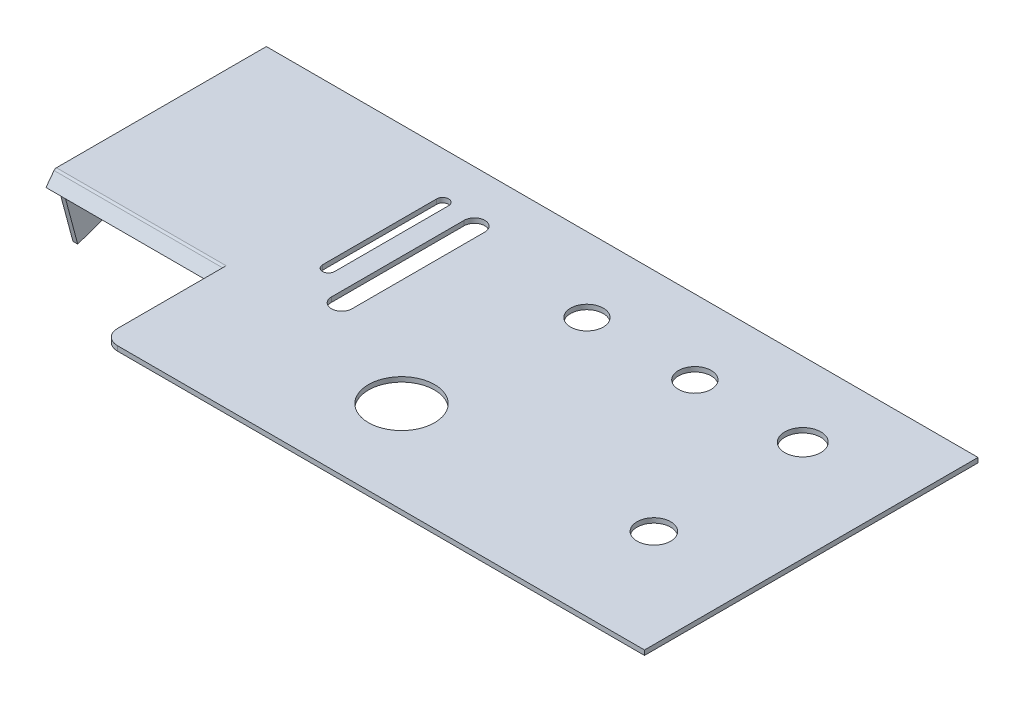
SolidWorks part; units mm, degrees
ref_plane "Front Plane" through (0, 0, 0) normal (0, 0, 1) x (1, 0, 0)
ref_plane "Top Plane" through (0, 0, 0) normal (0, 1, 0) x (1, 0, 0)
ref_plane "Right Plane" through (0, 0, 0) normal (1, 0, 0) x (0, 0, -1)
sketch "Sketch1" plane through (0, 0, 0) normal (0, 1, 0) x (1, 0, 0)
  line L0 (-101.3722, -12.5155) -> (-44.3722, -12.5155) construction
  line L1 (-44.3722, -53.5155) -> (137.6278, -53.5155) construction
  line L2 (-101.3722, -12.5155) -> (-101.3722, 58.4845) construction
  line L3 (-101.3722, 58.4845) -> (137.6278, 58.4845) construction
  line L4 (137.6278, -53.5155) -> (137.6278, 58.4845) construction
  line L5 (-44.3722, -12.5155) -> (-44.3722, -53.5155) construction
  line L6 (-26.4722, 42.7845) -> (-26.4722, 4.4845) construction
  line L7 (-23.4722, 42.7845) -> (-23.4722, 4.4845) construction
  line L8 (-29.4722, 42.7845) -> (-29.4722, 4.4845) construction
  line L9 (-14.1722, 41.1845) -> (-14.1722, -3.4155) construction
  line L10 (-9.5722, 41.1845) -> (-9.5722, -3.4155) construction
  line L11 (-18.7722, 41.1845) -> (-18.7722, -3.4155) construction
  line L12 (-26.4722, 45.7845) -> (-43.4588, 45.7845) construction
  line L13 (-26.4722, 1.4845) -> (-43.4588, 1.4845) construction
  line L14 (-14.1722, -8.0155) -> (-3.3024, -8.0155) construction
  line L15 (-14.1722, 45.7845) -> (0, 45.7845) construction
  line L16 (31.286, 33.4845) -> (122.5273, 33.4845) construction
  arc A0 (-23.4722, 42.7845) -> (-29.4722, 42.7845) centre (-26.4722, 42.7845) ccw construction
  arc A1 (-29.4722, 4.4845) -> (-23.4722, 4.4845) centre (-26.4722, 4.4845) ccw construction
  arc A2 (-9.5722, 41.1845) -> (-18.7722, 41.1845) centre (-14.1722, 41.1845) ccw construction
  arc A3 (-18.7722, -3.4155) -> (-9.5722, -3.4155) centre (-14.1722, -3.4155) ccw construction
  circle A7 centre (25.1778, -22.6655) radius 11.15 construction
  circle A8 centre (104.7278, -17.4655) radius 5.95 construction
  circle A9 centre (31.286, 33.4845) radius 6.25 construction
  circle A10 centre (67.536, 33.4845) radius 6.25 construction
  circle A11 centre (103.786, 33.4845) radius 6.25 construction
  point P0 (0, 0)
  point P10 (-26.4722, 23.6345)
  point P15 (-14.1722, 18.8845)
  dimension "D5" = 3
  dimension "D6" = 4.6
  dimension "D7" = 44.3
  dimension "D9" = 12.5
  dimension "D10" = 22.3
  dimension "D11" = 11.9
  dimension "D14" = 149.1
  dimension "D16" = 12.7
  dimension "D19" = 81.15
  dimension "D1" = 239
  dimension "D2" = 182
  dimension "D3" = 74.9
  dimension "D4" = 87.2
  dimension "D8" = 53.8
  dimension "D12" = 112
  dimension "D13" = 69.55
  dimension "D15" = 12.7
  dimension "D17" = 25
  dimension "D20" = 75.95
  dimension "D21" = 71
  dimension "D22" = 41
  dimension "D18" = 3
sketch "Sketch2" plane through (0, 0, 0) normal (0, 1, 0) x (1, 0, 0)
  line L0 (-101.3722, -12.5155) -> (-44.3722, -12.5155)
  line L1 (-101.3722, 58.4845) -> (137.6278, 58.4845)
  line L2 (-101.3722, 58.4845) -> (-101.3722, -12.5155)
  line L3 (-39.3722, -53.5155) -> (137.6278, -53.5155)
  line L4 (137.6278, 58.4845) -> (137.6278, -53.5155)
  line L5 (-44.3722, -12.5155) -> (-44.3722, -48.5155)
  line L6 (-26.4722, 4.4845) -> (-26.4722, 42.7845) construction
  line L7 (-28.4722, 4.4845) -> (-28.4722, 42.7845)
  line L8 (-24.4722, 4.4845) -> (-24.4722, 42.7845)
  line L9 (-14.1722, 41.1845) -> (-14.1722, -3.4155) construction
  line L10 (-10.7222, 41.1845) -> (-10.7222, -3.4155)
  line L11 (-17.6222, 41.1845) -> (-17.6222, -3.4155)
  arc A0 (-28.4722, 4.4845) -> (-24.4722, 4.4845) centre (-26.4722, 4.4845) ccw
  arc A1 (-24.4722, 42.7845) -> (-28.4722, 42.7845) centre (-26.4722, 42.7845) ccw
  arc A2 (-10.7222, 41.1845) -> (-17.6222, 41.1845) centre (-14.1722, 41.1845) ccw
  arc A3 (-17.6222, -3.4155) -> (-10.7222, -3.4155) centre (-14.1722, -3.4155) ccw
  circle A4 centre (31.286, 33.4845) radius 5.5
  circle A5 centre (67.536, 33.4845) radius 5.5
  circle A6 centre (103.786, 33.4845) radius 6.05
  circle A7 centre (25.1778, -22.6655) radius 11.1
  circle A8 centre (104.7278, -17.4655) radius 5.65
  arc A11 (-44.3722, -48.5155) -> (-39.3722, -53.5155) centre (-39.3722, -48.5155) ccw
  point P15 (-26.4722, 23.6345)
  point P24 (-14.1722, 18.8845)
  point P50 (-44.3722, -53.5155)
  dimension "D1" = 2
  dimension "D2" = 3.45
  dimension "D3" = 11
  dimension "D4" = 11
  dimension "D5" = 12.1
  dimension "D6" = 22.2
  dimension "D7" = 11.3
  dimension "D8" = 5
extrude "Boss-Extrude1" add sketch "Sketch2" along normal blind 1.6
sketch "Sketch3" plane through (-44.3722, 0, 0) normal (-1, 0, 0) x (0, 0, 1)
  line L0 (12.5155, 1.6) -> (15.5155, -2.4)
  line L1 (15.5155, -2.4) -> (12.5155, -2.4)
  line L2 (12.5155, -2.4) -> (12.5155, 1.6)
  dimension "D1" = 3
  dimension "D2" = 4
extrude "Boss-Extrude2" add sketch "Sketch3" along normal blind 57
fillet "Fillet1" radius 1 1 edges at (-72.8722, 1.6, 12.5155)
sketch "Sketch5" plane through (-101.3722, 0, 0) normal (-1, 0, 0) x (0, 0, 1)
  line L0 (-58.4845, 0) -> (12.5155, 0)
  line L3 (12.5155, 0) -> (6.4591, -22.6027)
  line L4 (6.4591, -22.6027) -> (-58.4845, 0)
  dimension "D1" = 23.4
  dimension "D2" = 71
  dimension "D3" = 75
extrude "Boss-Extrude3" add sketch "Sketch5" against normal blind 1.6
